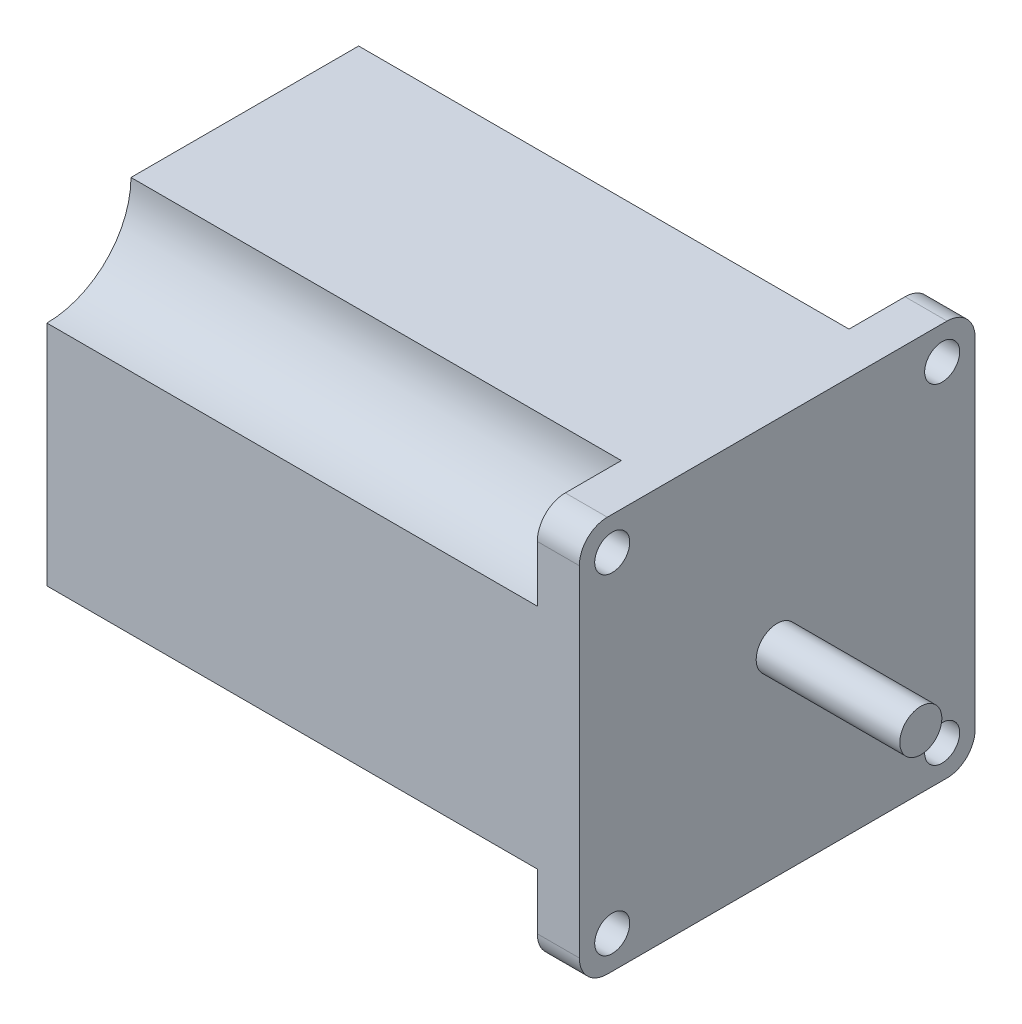
SolidWorks part; units mm, degrees
material "AISI 8620"
ref_plane "Front" through (0, 0, 0) normal (0, 0, 1) x (1, 0, 0)
ref_plane "Top" through (0, 0, 0) normal (0, 1, 0) x (1, 0, 0)
ref_plane "Right" through (0, 0, 0) normal (1, 0, 0) x (0, 0, -1)
ref_axis "Axis1" through (-26.25, 0, 0) along (1, 0, 0)
ref_axis "Axis2" through (0, 0, -21.0432) along (0, 0, 1)
ref_axis "Axis3" through (0, 23.0562, 0) along (0, -1, 0)
sketch "Sketch1" plane through (0, 0, 0) normal (1, 0, 0) x (0, 0, -1)
  line L0 (0, 15.9521) -> (0, 0) construction
  line L1 (-24.25, -28.25) -> (24.25, -28.25)
  line L2 (-28.25, -24.25) -> (-28.25, 24.25)
  line L3 (-24.25, 28.25) -> (24.25, 28.25)
  line L4 (28.25, -24.25) -> (28.25, 24.25)
  line L5 (-28.25, -28.25) -> (28.25, 28.25) construction
  line L6 (-28.25, 28.25) -> (28.25, -28.25) construction
  line L7 (0, 0) -> (15.3206, 0) construction
  arc A0 (-24.25, -28.25) -> (-28.25, -24.25) centre (-24.25, -24.25) cw
  arc A1 (24.25, 28.25) -> (28.25, 24.25) centre (24.25, 24.25) cw
  arc A2 (24.25, -28.25) -> (28.25, -24.25) centre (24.25, -24.25) ccw
  arc A3 (-28.25, 24.25) -> (-24.25, 28.25) centre (-24.25, 24.25) cw
  circle A4 centre (-23.55, 23.55) radius 2.5
  circle A5 centre (-23.55, -23.55) radius 2.5
  circle A6 centre (23.55, -23.55) radius 2.5
  circle A7 centre (23.55, 23.55) radius 2.5
  point P0 (0, 0)
  dimension "D2" = 4
  dimension "D3" = 47.1
  dimension "D4" = 47.1
  dimension "D5" = 5
  dimension "D1" = 56.5
extrude "Boss-Extrude1" add sketch "Sketch1" against normal blind 76
sketch "Sketch2" plane through (0, 0, 0) normal (0, 1, 0) x (1, 0, 0)
  line L0 (0, 0) -> (20.5, 0) construction
  line L1 (20.5, 0) -> (20.5, 3)
  line L2 (20.5, 3) -> (0, 3)
  line L5 (0, 3) -> (0, 0)
  line L6 (0, 0) -> (20.5, 0)
  dimension "D2" = 6
  dimension "D4" = 20.5
revolve "Revolve1" add sketch "Sketch2" angle 360 about L0
sketch "Sketch3" plane through (-76, 0, 0) normal (-1, 0, 0) x (0, 0, 1)
  line L0 (-28.25, -24.25) -> (-28.25, 24.25) construction
  line L1 (-24.25, 28.25) -> (24.25, 28.25) construction
  line L2 (28.25, 24.25) -> (28.25, -24.25) construction
  line L3 (24.25, -28.25) -> (-24.25, -28.25) construction
  line L4 (0, 17.853) -> (0, 0) construction
  line L5 (0, 0) -> (13.7606, 0) construction
  line L6 (-28.25, -16.25) -> (-28.25, -24.25)
  line L7 (-16.25, 28.25) -> (-24.25, 28.25)
  line L8 (28.25, 16.25) -> (28.25, 24.25)
  line L9 (16.25, -28.25) -> (24.25, -28.25)
  line L10 (28.25, -24.25) -> (28.25, 24.25)
  line L11 (24.25, 28.25) -> (-24.25, 28.25)
  line L12 (-28.25, 24.25) -> (-28.25, -24.25)
  line L13 (-24.25, -28.25) -> (24.25, -28.25)
  line L14 (28.25, -24.25) -> (28.25, -16.25)
  line L15 (24.25, 28.25) -> (16.25, 28.25)
  line L16 (-28.25, 24.25) -> (-28.25, 16.25)
  line L17 (-24.25, -28.25) -> (-16.25, -28.25)
  arc A0 (-28.25, 16.25) -> (-16.25, 28.25) centre (-28.25, 28.25) ccw
  arc A1 (16.25, 28.25) -> (28.25, 16.25) centre (28.25, 28.25) ccw
  arc A2 (-28.25, -16.25) -> (-16.25, -28.25) centre (-28.25, -28.25) cw
  arc A3 (28.25, -16.25) -> (16.25, -28.25) centre (28.25, -28.25) ccw
  arc A8 (24.25, -28.25) -> (28.25, -24.25) centre (24.25, -24.25) ccw
  arc A9 (28.25, 24.25) -> (24.25, 28.25) centre (24.25, 24.25) ccw
  arc A10 (-24.25, 28.25) -> (-28.25, 24.25) centre (-24.25, 24.25) ccw
  arc A11 (-28.25, -24.25) -> (-24.25, -28.25) centre (-24.25, -24.25) ccw
  arc A12 (24.25, -28.25) -> (28.25, -24.25) centre (24.25, -24.25) ccw
  arc A13 (28.25, 24.25) -> (24.25, 28.25) centre (24.25, 24.25) ccw
  arc A14 (-24.25, 28.25) -> (-28.25, 24.25) centre (-24.25, 24.25) ccw
  arc A15 (-28.25, -24.25) -> (-24.25, -28.25) centre (-24.25, -24.25) ccw
  dimension "D1" = 12
  dimension "D2" = 0
extrude "Cut-Extrude1" cut sketch "Sketch3" against normal offset from surface (70 mm away) 6 up to face at (0, 0, 3)
